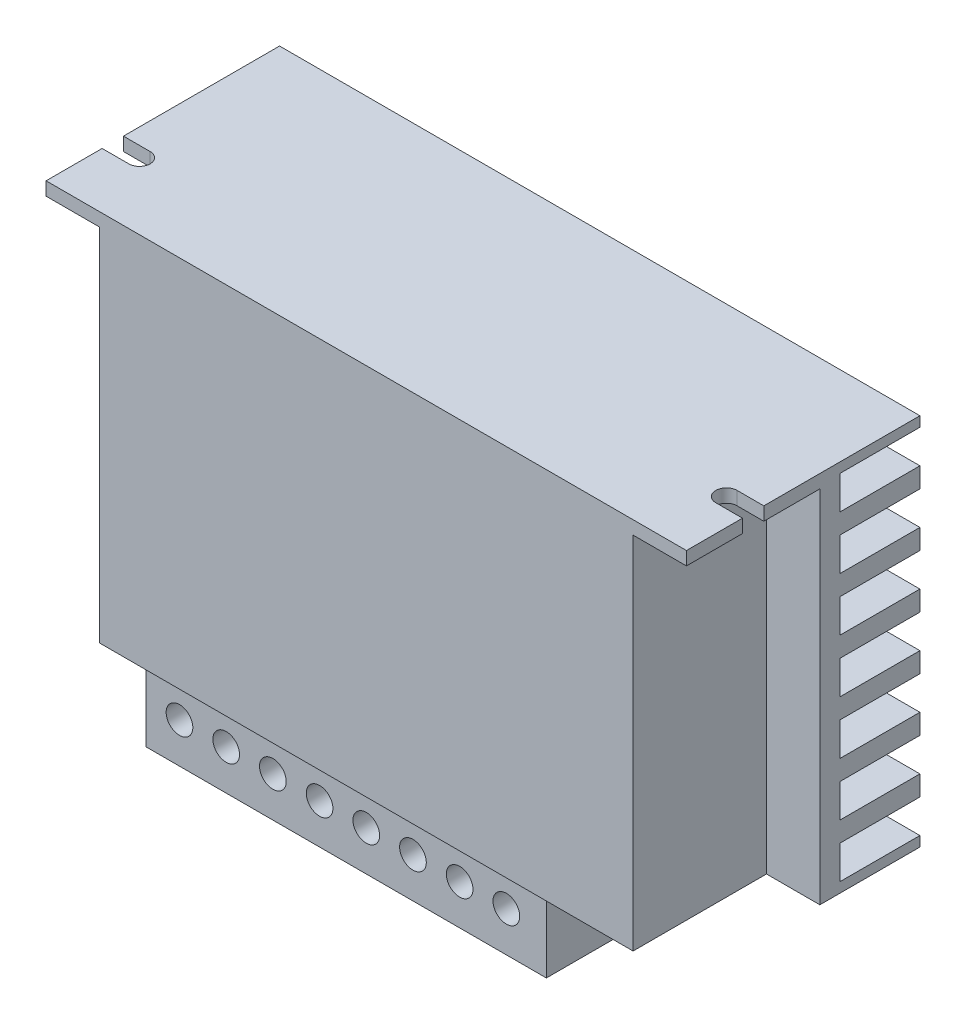
SolidWorks part; units mm, degrees
material "Простая углеродистая сталь"
ref_plane "Спереди" through (0, 0, 0) normal (0, 0, 1) x (1, 0, 0)
ref_plane "Сверху" through (0, 0, 0) normal (0, 1, 0) x (1, 0, 0)
ref_plane "Справа" through (0, 0, 0) normal (1, 0, 0) x (0, 0, -1)
sketch "Эскиз1" plane through (0, 0, 0) normal (0, 0, 1) x (1, 0, 0)
  line L0 (0, 0) -> (96, 0)
  line L1 (0, 0) -> (0, 56)
  line L2 (96, 0) -> (96, 56)
  line L3 (0, 56) -> (96, 56)
  dimension "D1" = 56
  dimension "D2" = 96
extrude "Бобышка-Вытянуть1" add sketch "Эскиз1" along normal blind 35
sketch "Эскиз5" plane through (96, 0, 0) normal (1, 0, 0) x (0, 0, -1)
  line L0 (-35, 54) -> (-15, 54)
  line L1 (-15, 54) -> (-15, 0)
  line L2 (-35, 56) -> (0, 56) construction
  line L3 (0, 0) -> (0, 56) construction
  line L4 (0, 0) -> (0, 56)
  line L5 (0, 56) -> (-35, 56)
  line L6 (-35, 56) -> (-35, 0)
  line L7 (-35, 0) -> (0, 0)
  line L10 (-35, 54) -> (-35, 0)
  line L11 (-35, 0) -> (-15, 0)
  dimension "D2" = 2
  dimension "D3" = 15
  dimension "D1" = 0
extrude "Вырез-Вытянуть3" cut sketch "Эскиз5" against normal blind 8
sketch "Эскиз6" plane through (0, 0, 0) normal (-1, 0, 0) x (0, 0, 1)
  line L4 (35, 0) -> (35, 54)
  line L5 (15, 0) -> (35, 0)
  line L6 (15, 54) -> (15, 0)
  line L7 (35, 54) -> (15, 54)
  line L8 (35, 0) -> (35, 54)
  line L9 (15, 0) -> (35, 0)
  line L10 (15, 54) -> (15, 0)
  line L11 (35, 54) -> (15, 54)
  dimension "D1" = 0
extrude "Вырез-Вытянуть4" cut sketch "Эскиз6" against normal blind 8
sketch "Эскиз7" plane through (96, 0, 0) normal (1, 0, 0) x (0, 0, -1)
  line L0 (-12, 1.5) -> (-12, 6.5)
  line L1 (-12, 1.5) -> (0, 1.5)
  line L2 (-12, 6.5) -> (0, 6.5)
  line L3 (0, 1.5) -> (0, 6.5)
  line L4 (0, 0) -> (0, 56) construction
  line L5 (-15, 0) -> (0, 0) construction
  line L6 (0, 9.5) -> (0, 14.5)
  line L7 (-12, 14.5) -> (0, 14.5)
  line L8 (-12, 9.5) -> (-12, 14.5)
  line L9 (-12, 9.5) -> (0, 9.5)
  line L10 (0, 17.5) -> (0, 22.5)
  line L11 (-12, 22.5) -> (0, 22.5)
  line L12 (-12, 17.5) -> (-12, 22.5)
  line L13 (-12, 17.5) -> (0, 17.5)
  line L14 (0, 25.5) -> (0, 30.5)
  line L15 (-12, 30.5) -> (0, 30.5)
  line L16 (-12, 25.5) -> (-12, 30.5)
  line L17 (-12, 25.5) -> (0, 25.5)
  line L18 (0, 33.5) -> (0, 38.5)
  line L19 (-12, 38.5) -> (0, 38.5)
  line L20 (-12, 33.5) -> (-12, 38.5)
  line L21 (-12, 33.5) -> (0, 33.5)
  line L22 (0, 41.5) -> (0, 46.5)
  line L23 (-12, 46.5) -> (0, 46.5)
  line L24 (-12, 41.5) -> (-12, 46.5)
  line L25 (-12, 41.5) -> (0, 41.5)
  line L26 (0, 49.5) -> (0, 54.5)
  line L27 (-12, 54.5) -> (0, 54.5)
  line L28 (-12, 49.5) -> (-12, 54.5)
  line L29 (-12, 49.5) -> (0, 49.5)
  line L30 (-35, 56) -> (0, 56) construction
  point P4 (-7.5, 0)
  dimension "D1" = 1.5
  dimension "D2" = 5
  dimension "D3" = 12
  dimension "D5" = 8
  dimension "D6" = 1.5
  dimension "D4" = 7
extrude "Вырез-Вытянуть5" cut sketch "Эскиз7" against normal through all
sketch "Эскиз8" plane through (0, 54, 0) normal (0, -1, 0) x (1, 0, 0)
  line L0 (88, 25) -> (96, 25) construction
  line L1 (88, 15) -> (88, 35) construction
  line L2 (96, 15) -> (96, 35) construction
  line L3 (92, 26.6) -> (96, 26.6)
  line L4 (96, 26.6) -> (96, 23.4)
  line L5 (96, 23.4) -> (92, 23.4)
  line L6 (96, 35) -> (0, 35) construction
  line L7 (48, 35) -> (48, 19.7888) construction
  line L8 (96, 26.6) -> (92, 26.6)
  line L9 (92, 23.4) -> (96, 23.4)
  line L10 (8, 25) -> (0, 25) construction
  line L11 (4, 23.4) -> (0, 23.4)
  line L12 (0, 26.6) -> (4, 26.6)
  line L13 (0, 23.4) -> (4, 23.4)
  line L14 (0, 26.6) -> (0, 23.4)
  line L15 (4, 26.6) -> (0, 26.6)
  arc A0 (92, 26.6) -> (92, 23.4) centre (92, 25) ccw
  arc A1 (4, 26.6) -> (4, 23.4) centre (4, 25) cw
  line M1 (96, 15) -> (96, 35)
  dimension "D1" = 3.2
extrude "Вырез-Вытянуть7" cut sketch "Эскиз8" against normal through all contours A1 L12 L14 L11 | L3 A0 L5 M1 region at (93.3596, 54, 25) region at (2.6404, 54, 25)
sketch "Эскиз9" plane through (0, 0, 0) normal (0, -1, 0) x (1, 0, 0)
  line L0 (13, 33) -> (73, 33)
  line L1 (13, 33) -> (13, 18)
  line L2 (73, 33) -> (73, 18)
  line L3 (13, 18) -> (73, 18)
  line L4 (8, 35) -> (88, 35) construction
  line L5 (8, 15) -> (8, 35) construction
  dimension "D1" = 2
  dimension "D2" = 5
  dimension "D3" = 60
  dimension "D4" = 15
extrude "Бобышка-Вытянуть2" add sketch "Эскиз9" along normal blind 12
sketch "Эскиз10" plane through (0, 0, 33) normal (0, 0, 1) x (1, 0, 0)
  line L0 (13, -6) -> (73, -6) construction
  line L1 (13, -12) -> (13, 0) construction
  line L2 (73, -12) -> (73, 0) construction
  line L3 (20, -6) -> (80, -6) construction
  line L4 (27, -6) -> (87, -6) construction
  line L5 (34, -6) -> (94, -6) construction
  line L6 (41, -6) -> (101, -6) construction
  line L7 (48, -6) -> (108, -6) construction
  line L8 (55, -6) -> (115, -6) construction
  line L9 (62, -6) -> (122, -6) construction
  circle A0 centre (18, -6) radius 2
  circle A1 centre (25, -6) radius 2
  circle A2 centre (32, -6) radius 2
  circle A3 centre (39, -6) radius 2
  circle A4 centre (46, -6) radius 2
  circle A5 centre (53, -6) radius 2
  circle A6 centre (60, -6) radius 2
  circle A7 centre (67, -6) radius 2
  dimension "D1" = 4
  dimension "D2" = 5
  dimension "D4" = 7
  dimension "D3" = 8
extrude "Вырез-Вытянуть8" cut sketch "Эскиз10" against normal blind 3
